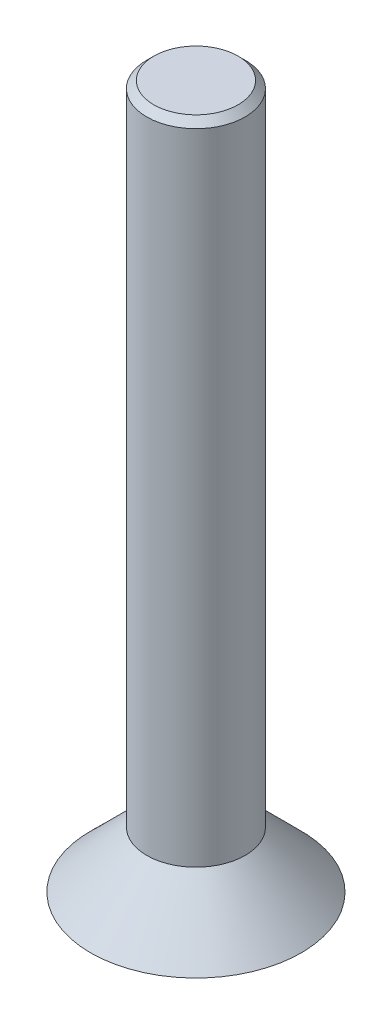
SolidWorks part; units mm, degrees
material "铸造合金钢"
ref_plane "前视基准面" through (0, 0, 0) normal (0, 0, 1) x (1, 0, 0)
ref_plane "上视基准面" through (0, 0, 0) normal (0, 1, 0) x (1, 0, 0)
ref_plane "右视基准面" through (0, 0, 0) normal (1, 0, 0) x (0, 0, -1)
sketch "草图1" plane through (0, 0, 0) normal (0, 1, 0) x (1, 0, 0)
  line L1 (0, -1.1547) -> (1, -0.5774)
  line L2 (1, -0.5774) -> (1, 0.5774)
  line L3 (1, 0.5774) -> (0, 1.1547)
  line L4 (0, 1.1547) -> (-1, 0.5774)
  line L5 (-1, 0.5774) -> (-1, -0.5774)
  line L6 (-1, -0.5774) -> (0, -1.1547)
  circle A0 centre (0, 0) radius 3
  circle A1 centre (0, 0) radius 1 construction
  dimension "D1" = 6
  dimension "D2" = 2
extrude "凸台-拉伸1" add sketch "草图1" along normal blind 1.6
chamfer "倒角1" distance 1.6 angle 45 1 edges at (0, 1.6, 3)
sketch "草图2" plane through (0, 1.6, 0) normal (0, 1, 0) x (1, 0, 0)
  circle A0 centre (0, 0) radius 1.4
  dimension "D1" = 2.8
extrude "凸台-拉伸2" add sketch "草图2" along normal blind 18.4
chamfer "倒角2" distance 0.2 angle 45 1 edges at (0, 20, 1.4)
